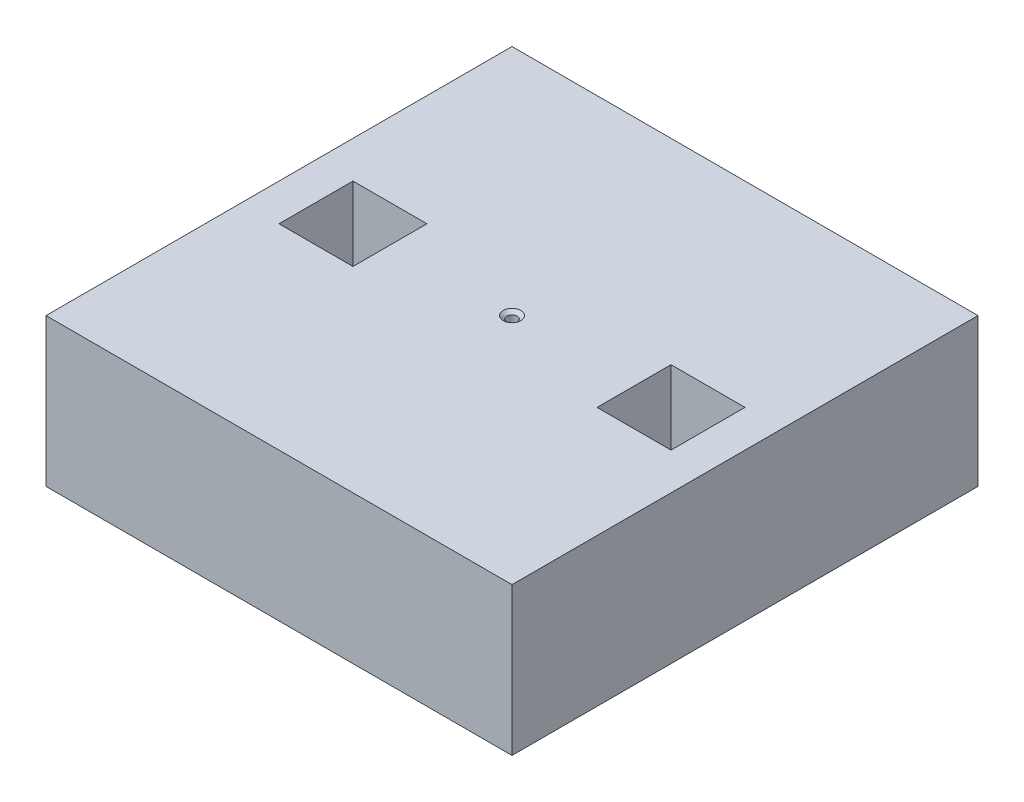
SolidWorks part; units mm, degrees
ref_plane "Front Plane" through (0, 0, 0) normal (0, 0, 1) x (1, 0, 0)
ref_plane "Top Plane" through (0, 0, 0) normal (0, 1, 0) x (1, 0, 0)
ref_plane "Right Plane" through (0, 0, 0) normal (1, 0, 0) x (0, 0, -1)
sketch "Sketch1" plane through (0, 0, 0) normal (0, 1, 0) x (1, 0, 0)
  line L0 (-40, 0) -> (40, 0) construction
  line L1 (-40, 40) -> (40, 40)
  line L2 (-40, 40) -> (-40, -40)
  line L3 (-40, -40) -> (40, -40)
  line L4 (40, 40) -> (40, -40)
  line L5 (-40, 40) -> (40, -40) construction
  line L6 (-40, -40) -> (40, 40) construction
  line L7 (-33.65, -6.35) -> (-20.95, -6.35)
  line L8 (-33.65, -6.35) -> (-33.65, 6.35)
  line L9 (-33.65, 6.35) -> (-20.95, 6.35)
  line L10 (-20.95, -6.35) -> (-20.95, 6.35)
  line L11 (-33.65, -6.35) -> (-20.95, 6.35) construction
  line L12 (-33.65, 6.35) -> (-20.95, -6.35) construction
  line L13 (20.95, 6.35) -> (33.65, 6.35)
  line L14 (20.95, 6.35) -> (20.95, -6.35)
  line L15 (20.95, -6.35) -> (33.65, -6.35)
  line L16 (33.65, 6.35) -> (33.65, -6.35)
  line L17 (20.95, 6.35) -> (33.65, -6.35) construction
  line L18 (20.95, -6.35) -> (33.65, 6.35) construction
  line L19 (0, 40) -> (0, -40) construction
  point P0 (0, 0)
  point P6 (-27.3, 0)
  point P11 (27.3, 0)
  dimension "D1" = 80
  dimension "D2" = 80
  dimension "D3" = 6.35
  dimension "D4" = 6.35
  dimension "D5" = 12.7
  dimension "D6" = 12.7
  dimension "D7" = 12.7
  dimension "D8" = 12.7
extrude "Boss-Extrude1" add sketch "Sketch1" along normal blind 25.4
hole_wizard "CSK for #0 Flat Head Machine Screw (100)1" positions "Sketch2" profile "Sketch3" countersink size "#0" standard "ANSI Inch" end condition through all
sketch "Sketch2" plane through (0, 25.4, 0) normal (0, 1, 0) x (1, 0, 0)
  point P0 (0, 0)
sketch "Sketch3" plane through (0, 25.4, 0) normal (1, 0, 0) x (0, 0, 1)
  line L0 (0, 0) -> (0, 25.4)
  line L1 (0, 25.4) -> (0.889, 25.4)
  line L2 (0.889, 25.4) -> (0.889, 0.5222)
  line L3 (0.889, 0.5222) -> (1.5113, 0)
  line L5 (1.5113, 0) -> (0, 0)
  line L6 (-0.889, 0.5222) -> (-1.5113, 0) construction
  line L11 (0, -6.35) -> (0, 107.95) construction
  dimension "Thru Hole Dia." = 1.778
  dimension "Thru Hole Depth" = 25.4
  dimension "Near C'Sink Dia." = 3.0226
  dimension "Near C'Sink Angle" = 100
